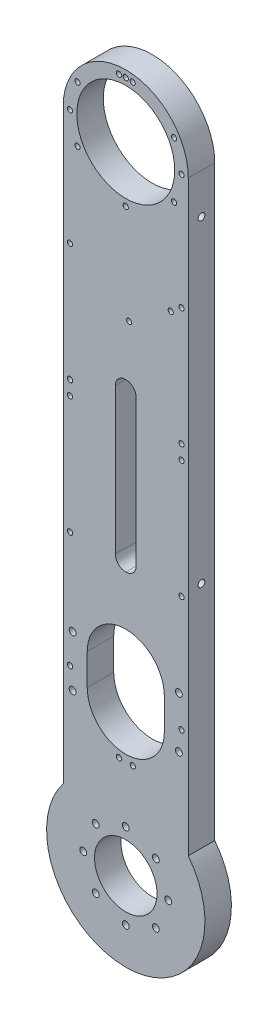
SolidWorks part; units mm, degrees
ref_plane "Front Plane" through (0, 0, 0) normal (0, 0, 1) x (1, 0, 0)
ref_plane "Top Plane" through (0, 0, 0) normal (0, 1, 0) x (1, 0, 0)
ref_plane "Right Plane" through (0, 0, 0) normal (1, 0, 0) x (0, 0, -1)
ref_plane "Plane1" through (0, 0, 12.7) normal (0, 0, 1) x (1, 0, 0)
sketch "Sketch1" plane through (0, 0, 12.7) normal (0, 0, 1) x (1, 0, 0)
  line L0 (-30, 305) -> (-30, 23.3238)
  line L1 (30, 23.3238) -> (30, 305)
  arc A0 (30, 305) -> (-30, 305) centre (0, 305) ccw
  arc A1 (-30, 23.3238) -> (30, 23.3238) centre (0, 0) ccw
extrude "Boss-Extrude1" add sketch "Sketch1" against normal blind 12.7
sketch "Sketch2" plane through (0, 0, 0) normal (0, 0, -1) x (-1, 0, 0)
  line L0 (18.5, 69.0225) -> (18.5, 84.0225)
  line L1 (-18.5, 84.0225) -> (-18.5, 69.0225)
  arc A0 (18.5, 84.0225) -> (-18.5, 84.0225) centre (0, 84.0225) ccw
  arc A1 (-18.5, 69.0225) -> (18.5, 69.0225) centre (0, 69.0225) ccw
  dimension "D1" = 15
  dimension "D2" = 69.0225
extrude "Cut-Extrude1" cut sketch "Sketch2" against normal through all
hole_wizard "Hole1" positions "Sketch4" profile "Sketch3" legacy
sketch "Sketch4" plane through (0, 0, 12.7) normal (0, 0, 1) x (1, 0, 0)
  point P0 (0, 0)
sketch "Sketch3" plane through (0, 0, 12.7) normal (1, 0, 0) x (0, -1, 0)
  line L0 (0, 0) -> (0, 12.7)
  line L1 (0, 12.7) -> (15, 12.7)
  line L2 (15, 12.7) -> (15, 0)
  line L3 (15, 0) -> (0, 0)
  line L4 (0, 110) -> (0, -10) construction
  dimension "Diameter" = 30
  dimension "Depth" = 12.7
hole_wizard "Hole2" positions "Sketch6" profile "Sketch5" legacy
sketch "Sketch6" plane through (0, 0, 12.7) normal (0, 0, 1) x (1, 0, 0)
  point P0 (0, 305)
sketch "Sketch5" plane through (0, 305, 12.7) normal (1, 0, 0) x (0, -1, 0)
  line L0 (0, 0) -> (0, 12.7)
  line L1 (0, 12.7) -> (23.5, 12.7)
  line L2 (23.5, 12.7) -> (23.5, 0)
  line L3 (23.5, 0) -> (0, 0)
  line L4 (0, 110) -> (0, -10) construction
  dimension "Diameter" = 47
  dimension "Depth" = 12.7
hole_wizard "#39 (0.0995) Diameter Hole1" positions "Sketch8" profile "Sketch7" hole size "#39" standard "ANSI Inch"
sketch "Sketch8" plane through (0, 0, 12.7) normal (0, 0, 1) x (1, 0, 0)
  point P0 (-26.75, 74.0225)
  point P1 (-26.75, 129.5112)
  point P2 (-26.75, 186.1112)
  point P3 (-26.75, 192.9112)
  point P4 (-26.75, 249.5112)
  point P5 (-26.75, 305)
  point P6 (-3.3, 331.5457)
  point P7 (3.3, 331.5457)
  point P8 (26.75, 305)
  point P9 (26.75, 249.5112)
  point P10 (26.75, 192.9112)
  point P11 (26.75, 186.1112)
  point P12 (26.75, 129.5112)
  point P13 (26.75, 74.0225)
  point P14 (3.4, 47.4894)
  point P15 (-3.3, 47.4768)
  point P16 (-23.1662, 318.375)
  point P17 (-23.1662, 291.625)
  point P18 (0, 278.25)
  point P19 (23.1662, 291.625)
  point P20 (23.1662, 318.375)
  point P21 (0, 331.75)
sketch "Sketch7" plane through (-26.75, 74.0225, 12.7) normal (1, 0, 0) x (0, -1, 0)
  line L0 (0, 0) -> (0, 12.7)
  line L1 (0, 12.7) -> (1.2636, 12.7)
  line L2 (1.2636, 12.7) -> (1.2636, 0)
  line L5 (1.2636, 0) -> (0, 0)
  line L11 (0, -6.35) -> (0, 107.95) construction
  dimension "Thru Hole Dia." = 2.5273
  dimension "Thru Hole Depth" = 12.7
hole_wizard "#4 Clearance Hole1" positions "Sketch10" profile "Sketch9" hole size "#4" standard "ANSI Inch"
sketch "Sketch10" plane through (0, 0, 0) normal (0, 0, -1) x (-1, 0, 0)
  line L0 (0, 102.5225) -> (0, 50.5225) construction
  arc A0 (18.5, 84.0225) -> (-18.5, 84.0225) centre (0, 84.0225) ccw construction
  arc A1 (-18.5, 69.0225) -> (18.5, 69.0225) centre (0, 69.0225) ccw construction
  point P2 (-25.5016, 64.2725)
  point P3 (-25.5016, 88.7725)
  point P4 (14.425, 14.425)
  point P5 (20.4, 0)
  point P6 (14.425, -14.425)
  point P7 (0, -20.4)
  point P8 (-14.425, -14.425)
  point P9 (-20.4, 0)
  point P10 (-14.425, 14.425)
  point P11 (0, 20.4)
  point P25 (25.5016, 64.2725)
  point P26 (25.5016, 88.7725)
  point P27 (0, 76.5225)
  dimension "D1" = 25.5016
  dimension "D2" = 25.5016
  dimension "D3" = 12.25
  dimension "D4" = 12.25
sketch "Sketch9" plane through (25.5016, 64.2725, 0) normal (1, 0, 0) x (0, 1, 0)
  line L0 (0, 0) -> (0, 12.7)
  line L1 (0, 12.7) -> (1.65, 12.7)
  line L2 (1.65, 12.7) -> (1.65, 0)
  line L5 (1.65, 0) -> (0, 0)
  line L11 (0, -6.35) -> (0, 107.95) construction
  dimension "Thru Hole Dia." = 3.3
  dimension "Thru Hole Depth" = 12.7
hole_wizard "#2 Clearance Hole1" positions "Sketch12" profile "Sketch11" hole size "#2" standard "ANSI Inch"
sketch "Sketch12" plane through (0, 0, 0) normal (0, 0, -1) x (-1, 0, 0)
  point P0 (-1.6199, 231.2653)
  point P1 (-21.5789, 245.4337)
sketch "Sketch11" plane through (1.6199, 231.2653, 0) normal (1, 0, 0) x (0, 1, 0)
  line L0 (0, 0) -> (0, 12.7)
  line L1 (0, 12.7) -> (1.25, 12.7)
  line L2 (1.25, 12.7) -> (1.25, 0)
  line L5 (1.25, 0) -> (0, 0)
  line L11 (0, -6.35) -> (0, 107.95) construction
  dimension "Thru Hole Dia." = 2.5
  dimension "Thru Hole Depth" = 12.7
hole_wizard "#4 Clearance Hole2" positions "Sketch14" profile "Sketch13" hole size "#4" standard "ANSI Inch"
sketch "Sketch14" plane through (30, 0, 0) normal (1, 0, 0) x (0, 0, -1)
  point P0 (-6.35, 285.7238)
  point P1 (-6.35, 133.3238)
sketch "Sketch13" plane through (30, 285.7238, 6.35) normal (0, 1, 0) x (0, 0, -1)
  line L0 (0, 0) -> (0, 10)
  line L1 (0, 10) -> (1.65, 10)
  line L2 (1.65, 10) -> (1.65, 0)
  line L5 (1.65, 0) -> (0, 0)
  line L10 (0, 10) -> (-1.65, 10) construction
  line L11 (0, -6.35) -> (0, 107.95) construction
  dimension "Hole Dia." = 3.3
  dimension "Hole Depth" = 10
  dimension "Drill Angle" = 180
sketch "草图1" plane through (0, 0, 0) normal (0, 0, -1) x (-1, 0, 0)
  line L1 (-5, 206.2653) -> (5, 206.2653)
  line L2 (-5, 206.2653) -> (-5, 126.2653)
  line L3 (-5, 126.2653) -> (5, 126.2653)
  line L4 (5, 206.2653) -> (5, 126.2653)
  line L7 (30, 305) -> (30, 23.3238) construction
  circle A0 centre (-1.6199, 231.2653) radius 1.25 construction
  dimension "D1" = 10
  dimension "D2" = 80
  dimension "D3" = 25
  dimension "D4" = 25
extrude "切除-拉伸1" cut sketch "草图1" against normal through all
fillet "圆角1" radius 5 4 edges at (-5, 126.2653, 6.35) (5, 126.2653, 6.35) (-5, 206.2653, 6.35) (5, 206.2653, 6.35)
